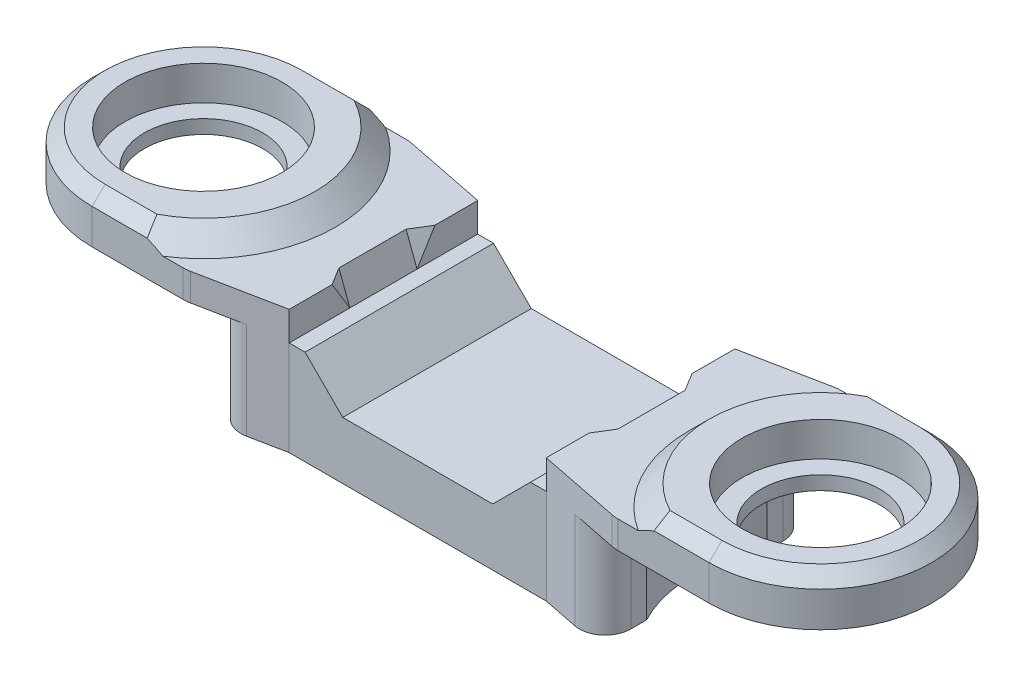
SolidWorks part; units mm, degrees
note: The reader was unsure of these and kept them because the rebuilt part matched: shared geometry of "Sketch1<5>", "Sketch1<6>", "Sketch1<7>", "Sketch1<8>", "Sketch2<4>".
ref_plane "Front" through (0, 0, 0) normal (0, 0, 1) x (1, 0, 0)
ref_plane "Top" through (0, 0, 0) normal (0, 1, 0) x (1, 0, 0)
ref_plane "Right" through (0, 0, 0) normal (1, 0, 0) x (0, 0, -1)
sketch "Sketch1" plane through (0, 0, 0) normal (0, 1, 0) x (1, 0, 0)
  line L0 (-18, 0) -> (18, 0) construction
  line L1 (0, 20.7126) -> (0, -16.4626) construction
  line L2 (-18, 6.5) -> (-12.5, 6.5)
  line L3 (-18, -6.5) -> (-12.5, -6.5)
  line L4 (-12.5, -6.5) -> (-7.5, -5.5)
  line L5 (-7.5, -5.5) -> (-7.5, 5.5)
  line L6 (-7.5, 5.5) -> (-12.5, 6.5)
  line L7 (-11.375, 6.275) -> (-11.375, 3.5156)
  line L8 (-11.375, -3.5156) -> (-11.375, -6.275)
  line L9 (11.375, -3.5156) -> (11.375, -6.275)
  line L10 (11.375, 6.275) -> (11.375, 3.5156)
  line L11 (18, -6.5) -> (12.5, -6.5)
  line L12 (12.5, -6.5) -> (7.5, -5.5)
  line L13 (7.5, 5.5) -> (12.5, 6.5)
  line L14 (18, 6.5) -> (12.5, 6.5)
  line L15 (-7.5, 5.5) -> (7.5, 5.5)
  line L16 (-7.5, -5.5) -> (7.5, -5.5)
  line L17 (7.5, -5.5) -> (7.5, 5.5)
  arc A0 (-11.375, -3.5156) -> (-11.375, 3.5156) centre (-18, 0) ccw
  circle A1 centre (-18, 0) radius 6.5
  circle A2 centre (-18, 0) radius 4.58
  circle A3 centre (-18, 0) radius 3.45
  arc A4 (-13.872, -6.5) -> (-13.872, 6.5) centre (-18, 0) ccw
  arc A5 (11.375, -3.5156) -> (11.375, 3.5156) centre (18, 0) cw
  arc A6 (13.872, -6.5) -> (13.872, 6.5) centre (18, 0) cw
  circle A7 centre (18, 0) radius 6.5
  circle A8 centre (18, 0) radius 4.58
  circle A9 centre (18, 0) radius 3.45
  dimension "D3" = 13
  dimension "D4" = 9.16
  dimension "D5" = 6.9
  dimension "D9" = 7.7
  dimension "D2" = 7.5
  dimension "D1" = 36
  dimension "D6" = 11
  dimension "D7" = 10.5
  dimension "D8" = 5.5
  dimension "D10" = 6.625
extrude "Boss-Extrude1" add sketch "Sketch1" along normal blind 5.545 contours L9 A6 L10 L13 L15 L6 L7 A4 L8 L4 L16 L12
extrude "Boss-Extrude2" add sketch "Sketch1<5>" along normal blind 7.245 contours A4 L7 L6 L2 | A4 L8 L4 L5 L6 L7 | A4 L3 L4 L8 | L10 A6 L14 L13 | L9 A6 L10 L13 L17 L12 | L11 A6 L9 L12
sketch "Sketch1<5>" plane through (0, 0, 0) normal (0, 1, 0) x (1, 0, 0) same geometry as "Sketch1"
extrude "Boss-Extrude3" add sketch "Sketch1<6>" along normal blind 8.445 contours L3 A4 L8 A0 L7 L2 A1 | A1 A2 | L11 A7 L14 A6 L10 A5 L9 | A7 A8 | A6 L9 A5 L10 | L8 A4 L7 A0
sketch "Sketch1<6>" plane through (0, 0, 0) normal (0, 1, 0) x (1, 0, 0) same geometry as "Sketch1"
extrude "Boss-Extrude4" add sketch "Sketch1<7>" along normal blind 6.445 contours A2 A3 | A8 A9
sketch "Sketch1<7>" plane through (0, 0, 0) normal (0, 1, 0) x (1, 0, 0) same geometry as "Sketch1"
extrude "Cut-Extrude1" cut sketch "Sketch1<8>" along normal blind 5.645 contours A1 A2 | A2 A3 | L3 A4 L8 A0 L7 L2 A1 | A4 L7 L6 L2 | A4 L3 L4 L8 | L10 A6 L14 L13 | L11 A6 L9 L12 | L11 A7 L14 A6 L10 A5 L9 | A7 A8 | A8 A9
sketch "Sketch1<8>" plane through (0, 0, 0) normal (0, 1, 0) x (1, 0, 0) same geometry as "Sketch1"
sketch "Sketch2" plane through (0, 0, 0) normal (0, 0, 1) x (1, 0, 0)
  line L0 (-8.1413, 7.245) -> (-7.5, 7.245)
  line L1 (-7.5, 7.245) -> (-7.5, 5.545)
  line L2 (-7.5, 5.545) -> (-8.1413, 7.245)
  line L3 (-7.5, 7.245) -> (-8.0614, 7.0332) construction
  line L10 (0, 13.5725) -> (0, -13.5725) construction
  line L14 (7.5, 5.545) -> (8.1413, 7.245)
  line L15 (7.5, 7.245) -> (7.5, 5.545)
  line L16 (8.1413, 7.245) -> (7.5, 7.245)
  line L20 (-4.375, 5.545) -> (-4.375, 3.345)
  line L22 (-4.375, 3.345) -> (4.375, 3.345)
  line L23 (4.375, 3.345) -> (4.375, 5.545)
  line L24 (4.375, 5.545) -> (-4.375, 5.545)
  dimension "D1" = 0.6
  dimension "D2" = 8.75
  dimension "D3" = 2.2
extrude "Cut-Extrude2" cut sketch "Sketch2" against normal mid plane 6 contours L2 L1 L0 | L14 L16 L15
extrude "Cut-Extrude3" cut sketch "Sketch2<4>" against normal through all both and the other way through all contours L23 L24 L20 L22
sketch "Sketch2<4>" plane through (0, 0, 0) normal (0, 0, 1) x (1, 0, 0) same geometry as "Sketch2"
chamfer "Chamfer1" distance 0.6 angle 60 4 edges at (7.8206, 6.395, 3) (7.8206, 6.395, -3) (-7.8206, 6.395, 3) (-7.8206, 6.395, -3)
chamfer "Chamfer2" distance 2.2 angle 45 2 edges at (4.375, 5.545, 0) (-4.375, 5.545, 0)
chamfer "Chamfer3" distance 0.75 angle 45 6 edges at (-15.936, 8.445, -6.5) (-15.936, 8.445, 6.5) (-24.5, 8.445, 0) (15.936, 8.445, -6.5) (15.936, 8.445, 6.5) (24.5, 8.445, 0)
chamfer "Chamfer4" distance 1.2 angle 45 2 edges at (-10.3, 8.445, 0) (10.3, 8.445, 0)
fillet "Fillet1" radius 2 4 edges at (12.5, 6.445, -6.5) (12.5, 6.445, 6.5) (-12.5, 6.445, -6.5) (-12.5, 6.445, 6.5)
fillet "Fillet2" radius 1.5 4 edges at (11.375, 2.8225, 6.275) (11.375, 2.8225, -6.275) (-11.375, 2.8225, 6.275) (-11.375, 2.8225, -6.275)
equation "\"L\"=36"
equation "\"D1@Sketch1\"=\"L\""
